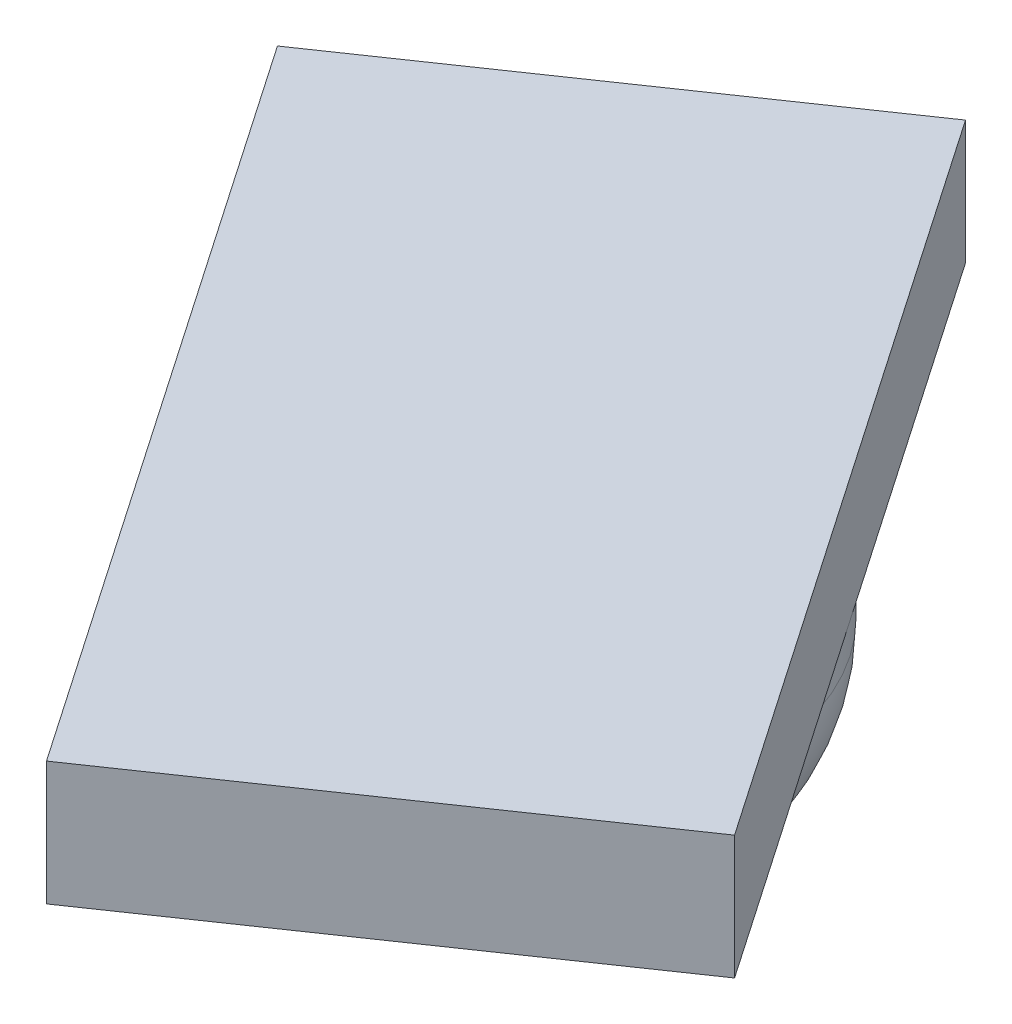
SolidWorks part; units mm, degrees
ref_plane "Front Plane" through (0, 0, 0) normal (0, 0, 1) x (1, 0, 0)
ref_plane "Top Plane" through (0, 0, 0) normal (0, 1, 0) x (1, 0, 0)
ref_plane "Right Plane" through (0, 0, 0) normal (1, 0, 0) x (0, 0, -1)
sketch "Sketch1" plane through (0, 0, 0) normal (0, 1, 0) x (1, 0, 0)
  circle A1 centre (0, 0) radius 4
extrude "Boss-Extrude1" add sketch "Sketch1" along normal blind 5.5
sketch "Sketch2" plane through (0, 5.5, 0) normal (0, 1, 0) x (1, 0, 0)
  line L0 (0.7726, -8.2002) -> (7.3706, -3.6762)
  line L1 (0.7726, -8.2002) -> (-7.3706, 3.6762)
  line L2 (7.3706, -3.6762) -> (-0.7726, 8.2002)
  line L3 (-7.3706, 3.6762) -> (-0.7726, 8.2002)
  line L4 (0.7726, -8.2002) -> (-0.7726, 8.2002) construction
  line L5 (7.3706, -3.6762) -> (-7.3706, 3.6762) construction
  point P1 (0, 0)
  dimension "D1" = 14.4
  dimension "D2" = 8
extrude "Boss-Extrude2" add sketch "Sketch2" against normal blind 2
fillet "Fillet3" radius 3 1 edges at (0, 0, 4)
